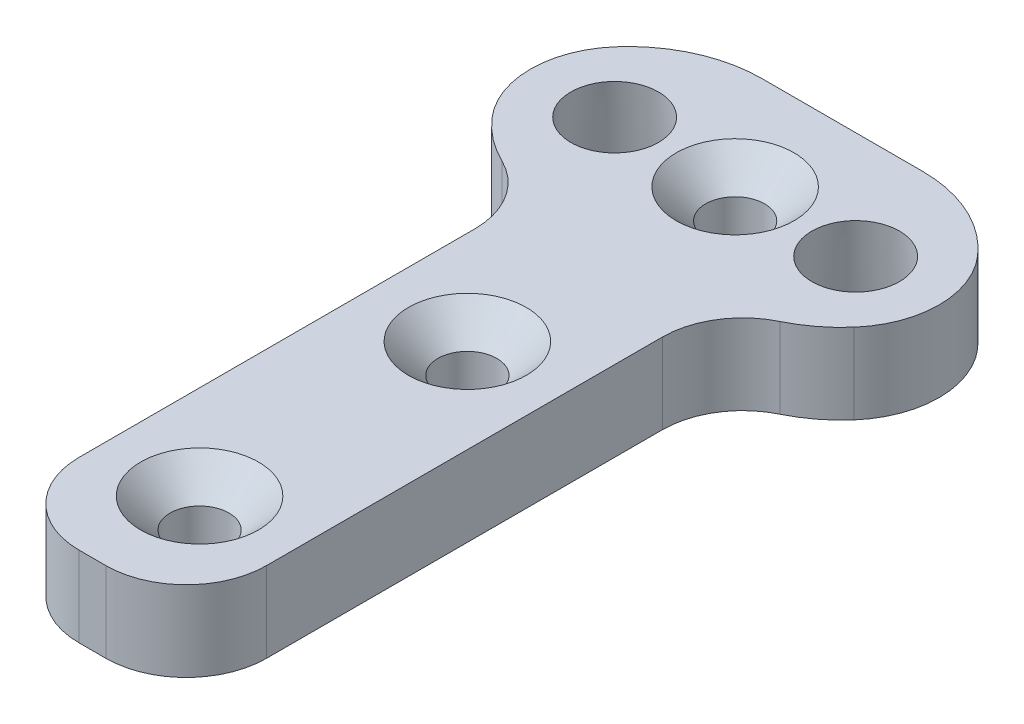
SolidWorks part; units mm, degrees
ref_plane "Front" through (0, 0, 0) normal (0, 0, 1) x (1, 0, 0)
ref_plane "Top" through (0, 0, 0) normal (0, 1, 0) x (1, 0, 0)
ref_plane "Right" through (0, 0, 0) normal (1, 0, 0) x (0, 0, -1)
sketch "Sketch1" plane through (0, 0, 0) normal (0, 1, 0) x (1, 0, 0)
  line L0 (3.5, 6) -> (8, 6)
  line L2 (-3.5, 6) -> (-3.5, -14)
  line L3 (-3.5, -14) -> (3.5, -14)
  line L4 (3.5, 6) -> (3.5, -14)
  line L5 (-8, 14) -> (8, 14)
  line L6 (-8, 14) -> (-8, 6)
  line L7 (-8, 6) -> (-3.5, 6)
  line L8 (8, 14) -> (8, 6)
  line L9 (0, 14) -> (0, -14) construction
  line L10 (-3.5, 6) -> (3.5, 6) construction
  point P10 (0, 0)
  point P12 (0, -14)
  point P13 (0, 6)
  dimension "D1" = 8
  dimension "D2" = 20
  dimension "D3" = 16
  dimension "D4" = 7
extrude "Boss-Extrude1" add sketch "Sketch1" along normal blind 3
sketch "Sketch2" plane through (0, 0, 0) normal (0, 1, 0) x (1, 0, 0)
  line L0 (0, 14) -> (0, -14) construction
  line L1 (8, 14) -> (-8, 14) construction
  line L2 (-3.5, -14) -> (3.5, -14) construction
  line L3 (-8, 10) -> (8, 10) construction
  line L4 (-8, 14) -> (-8, 6) construction
  line L5 (8, 6) -> (8, 14) construction
  circle A0 centre (0, 10) radius 0.5
  circle A1 centre (0, 0) radius 0.5
  circle A2 centre (0, -10) radius 0.5
  circle A3 centre (-4.5, 10) radius 0.5
  circle A4 centre (4.5, 10) radius 0.5
  dimension "D1" = 3.5
  dimension "D3" = 1
  dimension "D2" = 3.5
  dimension "D4" = 10
  dimension "D5" = 4
hole_wizard "CSK for M2 Countersunk Flat Head Screw3" positions "Sketch3" profile "Sketch4" countersink size "M2" standard "ISO"
sketch "Sketch3" plane through (0, 3, 0) normal (0, 1, 0) x (1, 0, 0)
  point P0 (0, 10)
  point P3 (0, 0)
  point P6 (0, -10)
sketch "Sketch4" plane through (0, 3, -10) normal (1, 0, 0) x (0, 0, 1)
  line L0 (0, 0) -> (0, 3.6609)
  line L1 (0, 3.6609) -> (1.1, 3)
  line L2 (1.1, 3) -> (1.1, 1.1)
  line L3 (1.1, 1.1) -> (2.2, 0)
  line L5 (2.2, 0) -> (0, 0)
  line L6 (-1.1, 1.1) -> (-2.2, 0) construction
  line L10 (0, 3.6609) -> (-1.1, 3) construction
  line L11 (0, -6.35) -> (0, 107.95) construction
  dimension "Hole Dia." = 2.2
  dimension "Hole Depth" = 3
  dimension "Near C'Sink Dia." = 4.4
  dimension "Near C'Sink Angle" = 90
  dimension "Drill Angle" = 118
fillet "Fillet1" radius 5 4 edges at (-8, 1.5, -6) (-8, 1.5, -14) (8, 1.5, -6) (8, 1.5, -14)
fillet "Fillet2" radius 3.5 2 edges at (7.9015, 1.5, -9.9875) (-7.9015, 1.5, -9.9875)
fillet "Fillet3" radius 3 4 edges at (-3.5, 1.5, -6) (3.5, 1.5, -6) (-3.5, 1.5, 14) (3.5, 1.5, 14)
hole_wizard "CSK for M2 Countersunk Flat Head Screw2" positions "Sketch7" profile "Sketch8" countersink size "M2" standard "ISO" end condition through all
sketch "Sketch7" plane through (0, 0, 0) normal (0, -1, 0) x (-1, 0, 0)
  point P0 (4.5, 10)
  point P3 (-4.5, 10)
sketch "Sketch8" plane through (-4.5, 0, -10) normal (1, 0, 0) x (0, 0, -1)
  line L0 (0, 0) -> (0, 3)
  line L1 (0, 3) -> (1.6, 3)
  line L2 (1.6, 3) -> (1.6, 3.3753)
  line L3 (1.6, 3.3753) -> (1.925, 0)
  line L5 (1.925, 0) -> (0, 0)
  line L6 (-1.6, 3.3753) -> (-1.925, 0) construction
  line L11 (0, -6.35) -> (0, 107.95) construction
  dimension "Thru Hole Dia." = 3.2
  dimension "Thru Hole Depth" = 3
  dimension "Near C'Sink Dia." = 3.85
  dimension "Near C'Sink Angle" = 11
